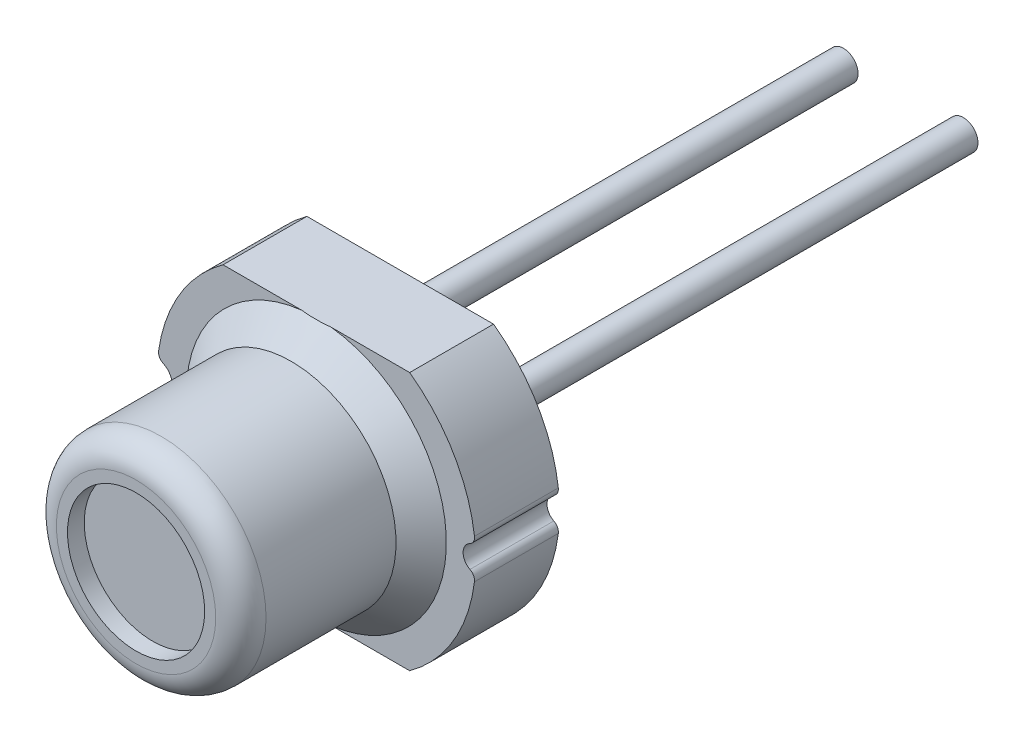
SolidWorks part; units mm, degrees
ref_plane "Front Plane" through (0, 0, 0) normal (0, 0, 1) x (1, 0, 0)
ref_plane "Top Plane" through (0, 0, 0) normal (0, 1, 0) x (1, 0, 0)
ref_plane "Right Plane" through (0, 0, 0) normal (1, 0, 0) x (0, 0, -1)
sketch "Sketch1" plane through (0, 0, 0) normal (0, 0, 1) x (1, 0, 0)
  line L0 (-1.1128, 1.54) -> (1.1128, 1.54)
  line L1 (-1.1128, -1.54) -> (1.1128, -1.54)
  arc A0 (-1.1128, 1.54) -> (-1.881, 0.268) centre (0, 0) ccw
  arc A1 (1.1128, -1.54) -> (1.8854, -0.235) centre (0, 0) ccw
  arc A2 (-1.8241, -0.1632) -> (-1.8241, 0.1632) centre (-1.9, 0) ccw
  arc A3 (1.8317, 0.1336) -> (1.8317, -0.1336) centre (1.9, 0) ccw
  arc A4 (-1.881, -0.268) -> (-1.1128, -1.54) centre (0, 0) ccw
  arc A5 (1.8854, 0.235) -> (1.1128, 1.54) centre (0, 0) ccw
  arc A6 (1.8317, -0.1336) -> (1.8854, -0.235) centre (1.7862, -0.2226) cw
  arc A7 (1.8317, 0.1336) -> (1.8854, 0.235) centre (1.7862, 0.2226) ccw
  arc A8 (-1.8241, -0.1632) -> (-1.881, -0.268) centre (-1.782, -0.2539) ccw
  arc A9 (-1.8241, 0.1632) -> (-1.881, 0.268) centre (-1.782, 0.2539) cw
  point P16 (1.8941, 0.1499)
  point P19 (-1.8915, -0.1798)
  dimension "D1" = 3.8
  dimension "D4" = 0.36
  dimension "D5" = 0.3
  dimension "D6" = 0.1
  dimension "D2" = 1.54
  dimension "D3" = 1.54
extrude "Boss-Extrude1" add sketch "Sketch1" along normal blind 1
sketch "Sketch3" plane through (0, 0, 1) normal (0, 0, 1) x (1, 0, 0)
  circle A0 centre (0, 0) radius 1.25
  dimension "D1" = 2.5
extrude "Boss-Extrude2" add sketch "Sketch3" along normal blind 2.15 contours A0
chamfer "Chamfer1" distance 0.3 angle 45 1 edges at (1.25, 0, 1)
fillet "Fillet1" radius 0.3 1 edges at (1.25, 0, 3.15)
sketch "Sketch4" plane through (0, 0, 3.15) normal (0, 0, 1) x (1, 0, 0)
  circle A0 centre (0, 0) radius 0.818
extrude "Cut-Extrude1" cut sketch "Sketch4" against normal blind 0.2
sketch "Sketch5" plane through (0, 0, 0) normal (0, 0, 1) x (1, 0, 0)
  circle A0 centre (0.715, 0.3) radius 0.175
  circle A1 centre (-0.715, 0.3) radius 0.175
  circle A2 centre (0, -0.415) radius 0.175
  circle A3 centre (0, 0.3) radius 0.715 construction
  point P9 (0, 0.4544)
  point P11 (0.715, 0.3)
  point P12 (-0.715, 0.3)
  point P13 (0, -0.415)
  dimension "D1" = 1.43
  dimension "D3" = 0.35
  dimension "D4" = 0.35
  dimension "D5" = 0.35
  dimension "D2" = 0.3
extrude "Boss-Extrude3" add sketch "Sketch5" against normal blind 6
sketch "Sketch6" plane through (0, 0, 0) normal (0, 0, -1) x (-1, 0, 0)
  circle A0 centre (0, -0.415) radius 0.3402
extrude "Boss-Extrude4" add sketch "Sketch6" along normal blind 0.2
